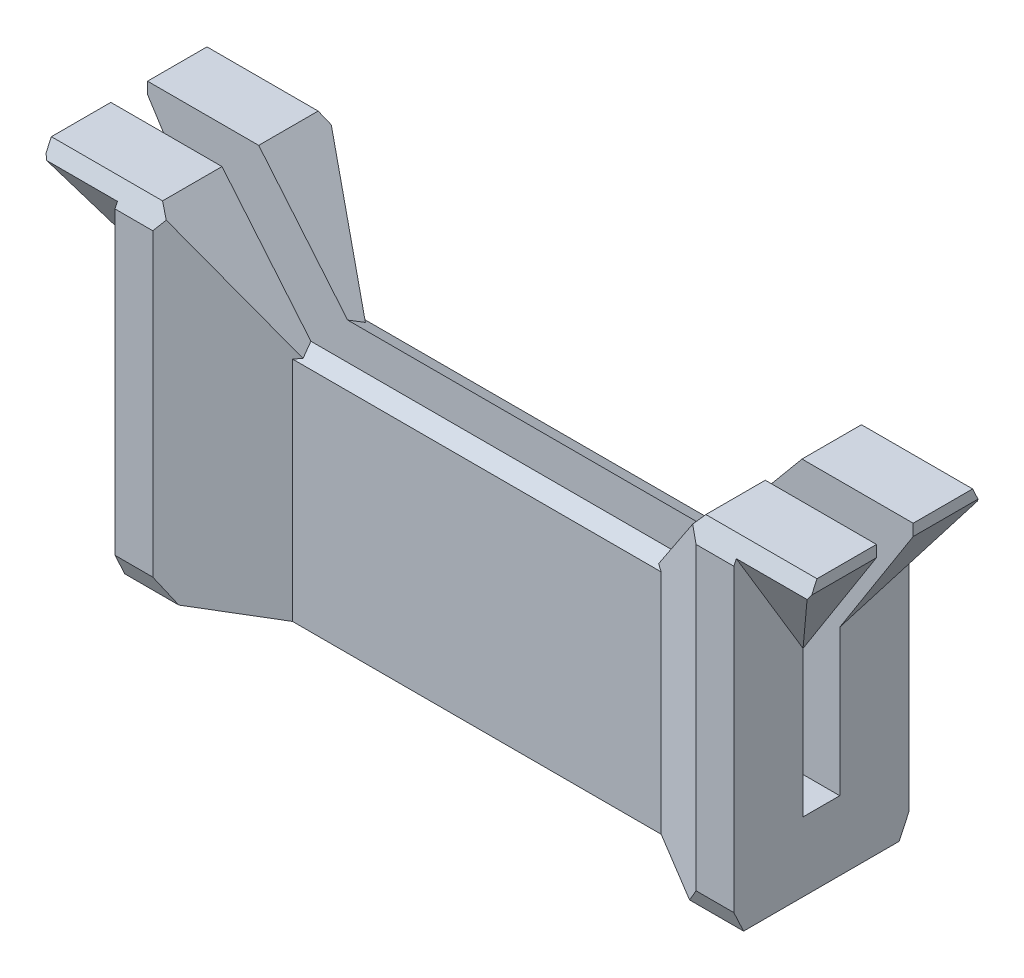
SolidWorks part; units mm, degrees
material "ABS"
ref_plane "Alzado" through (0, 0, 0) normal (0, 0, 1) x (1, 0, 0)
ref_plane "Planta" through (0, 0, 0) normal (0, 1, 0) x (1, 0, 0)
ref_plane "Vista lateral" through (0, 0, 0) normal (1, 0, 0) x (0, 0, -1)
sketch "Croquis2" plane through (0, 0, 0) normal (1, 0, 0) x (0, 0, -1)
  line L0 (-0.875, 0) -> (0.875, 0)
  line L1 (0.875, 0) -> (0.875, 13)
  line L2 (0.875, 13) -> (4.175, 13)
  line L3 (4.175, 13) -> (4.175, 2.1921)
  line L4 (4.175, 2.1921) -> (0.875, -3.3)
  line L5 (-0.875, -3.3) -> (0.875, -3.3)
  line L6 (0, -3.3) -> (0, 0) construction
  line L7 (-4.175, 2.1921) -> (-0.875, -3.3)
  line L8 (-4.175, 13) -> (-4.175, 2.1921)
  line L9 (-0.875, 13) -> (-4.175, 13)
  line L10 (-0.875, 0) -> (-0.875, 13)
  line L11 (4.175, 2.1921) -> (4.175, -3.3)
  line L12 (4.175, -3.3) -> (0.875, -3.3)
  line L13 (-0.875, -3.3) -> (-4.175, -3.3)
  line L14 (-4.175, -3.3) -> (-4.175, 2.1921)
  dimension "D1" = 1.75
  dimension "D3" = 13
  dimension "D4" = 62
  dimension "D5" = 1.75
  dimension "D6" = 3.3
extrude "Saliente-Extruir1" add sketch "Croquis2" along normal mid plane 36.5 contours L6 L5 L4 L3 L2 L1 L0 | L5 L6 L0 L10 L9 L8 L7 | L14 L13 L7 | L12 L11 L4
sketch "Croquis3" plane through (18.25, 0, 0) normal (1, 0, 0) x (0, 0, -1)
  line L0 (0.6, 1) -> (-0.6, 1)
  line L1 (-0.6, 1) -> (-0.6, 6.5)
  line L2 (-0.6, 6.5) -> (-4.175, 12.4498)
  line L3 (-4.175, 12.4498) -> (-4.175, 13)
  line L4 (-4.175, 13) -> (-4.175, -3.3) construction
  line L5 (-0.875, 0) -> (0.875, 0) construction
  line L6 (-4.175, 13) -> (-4.175, -3.3)
  line L8 (-4.175, -3.3) -> (4.175, -3.3)
  line L10 (0, -3.3) -> (0, 1) construction
  line L12 (4.175, 13) -> (4.175, -3.3)
  line L14 (4.175, 12.4498) -> (4.175, 13)
  line L15 (0.6, 6.5) -> (4.175, 12.4498)
  line L16 (0.6, 1) -> (0.6, 6.5)
  line M23 (0.875, 0) -> (-0.875, 0)
  line M24 (-0.875, 0) -> (-0.875, 13)
  line M26 (-4.175, 13) -> (-4.175, -3.3)
  line M27 (-4.175, -3.3) -> (4.175, -3.3)
  line M28 (4.175, -3.3) -> (4.175, 13)
  line M30 (0.875, 13) -> (0.875, 0)
  dimension "D1" = 1.2
  dimension "D2" = 5.5
  dimension "D3" = 1
  dimension "D4" = 62
extrude "Cortar-Extruir1" cut sketch "Croquis3" against normal blind 1.7 from offset 1.8 contours L10 L2 M27 M23 M24 M26 | L10 L8 L15 M28 M30 M23 offset against normal yes
mirror "Simetría1" about plane through (0, 0, 0) normal (1, 0, 0) of "Cortar-Extruir1"
sketch "Croquis4" plane through (0, 13, 0) normal (0, 1, 0) x (1, 0, 0)
  line L0 (8.7893, -1.675) -> (-8.7893, -1.675)
  line L1 (-8.7893, -1.675) -> (-12.95, -4.175)
  line L2 (18.25, -4.175) -> (-18.25, -4.175) construction
  line L3 (-12.95, -4.175) -> (12.95, -4.175)
  line L4 (0, -4.175) -> (0, -1.675) construction
  line L5 (8.7893, -1.675) -> (12.95, -4.175)
  line L6 (0, 0) -> (5.3382, 0) construction
  line L7 (8.7893, 1.675) -> (12.95, 4.175)
  line L8 (-12.95, 4.175) -> (12.95, 4.175)
  line L9 (-8.7893, 1.675) -> (-12.95, 4.175)
  line L10 (8.7893, 1.675) -> (-8.7893, 1.675)
  line L11 (18.25, -0.875) -> (-18.25, -0.875) construction
  line L12 (-12.95, -4.175) -> (23.55, -4.175) construction
  line L13 (18.25, -4.175) -> (-18.25, -4.175) construction
  line L14 (-12.95, -4.175) -> (-14.75, -4.175) construction
  line L15 (18.25, -4.175) -> (-18.25, -4.175) construction
  line L16 (-16.45, -4.175) -> (-18.25, -4.175) construction
  dimension "D1" = 0.8
  dimension "D2" = 62
extrude "Cortar-Extruir2" cut sketch "Croquis4" against normal through all
sketch "Croquis5" plane through (0, 0, 4.175) normal (0, 0, 1) x (1, 0, 0)
  line L0 (-12.95, 13) -> (12.95, 13)
  line L1 (0, 13) -> (0, 8) construction
  line L2 (8.7893, 8) -> (-8.7893, 8)
  line L3 (-8.7893, 8) -> (-12.95, 13)
  line L4 (-8.7893, -3.3) -> (-8.7893, 13) construction
  line L5 (8.7893, 8) -> (12.95, 13)
  dimension "D1" = 5
extrude "Cortar-Extruir3" cut sketch "Croquis5" against normal through all
sketch "Croquis6" plane through (14.75, 0, 0) normal (1, 0, 0) x (0, 0, -1)
  line L8 (-4.175, -3.3) -> (4.175, -3.3)
  line L9 (-4.175, -3.3) -> (4.175, -3.3)
  line L10 (4.175, 12.4498) -> (0.875, 6.9577)
  line L11 (0.875, 6.9577) -> (0.875, 0)
  line L12 (0.875, 0) -> (-0.875, 0)
  line L13 (-0.875, 0) -> (-0.875, 6.9577)
  line L14 (-0.875, 6.9577) -> (-4.175, 12.4498)
  line L15 (4.175, -3.3) -> (4.175, 12.4498)
  line L16 (4.175, -3.3) -> (4.175, 12.4498)
  line L17 (-4.175, 12.4498) -> (-4.175, -3.3)
  line L18 (4.175, 12.4498) -> (0.875, 6.9577)
  line L19 (0.875, 6.9577) -> (0.875, 0)
  line L20 (0.875, 0) -> (-0.875, 0)
  line L21 (-0.875, 0) -> (-0.875, 6.9577)
  line L22 (-0.875, 6.9577) -> (-4.175, 12.4498)
  line L23 (-4.175, 12.4498) -> (-4.175, -3.3)
  dimension "D1" = 0
extrude "Cortar-Extruir4" cut sketch "Croquis6" along normal up to next
mirror "Simetría2" about plane through (0, 0, 0) normal (1, 0, 0) of "Cortar-Extruir4"
sketch "Croquis7" plane through (0, 0, -4.175) normal (0, 0, -1) x (-1, 0, 0)
  line L0 (14.75, 6.9577) -> (18.25, 12.4498)
  line L1 (18.25, 12.4498) -> (18.25, 6.9577)
  line L2 (18.25, 6.9577) -> (14.75, 6.9577)
  line L4 (0, 0) -> (0, 13.5433) construction
  line L5 (-18.25, 6.9577) -> (-14.75, 6.9577)
  line L6 (-18.25, 12.4498) -> (-18.25, 6.9577)
  line L7 (-14.75, 6.9577) -> (-18.25, 12.4498)
extrude "Cortar-Extruir5" cut sketch "Croquis7" against normal blind 10
chamfer "Chaflán2" distance 1 angle 25 10 edges at (0, 8, 1.675) (0, 8, -1.675) (15.6, 13, 4.175) (-15.6, 13, 4.175) (-15.6, 13, -4.175) (15.6, 13, -4.175) (-13.85, -3.3, -4.175) (-13.85, -3.3, 4.175) (13.85, -3.3, 4.175) (13.85, -3.3, -4.175)
sketch "Croquis8" plane through (-14.75, 0, 0) normal (-1, 0, 0) x (0, 0, 1)
  line L0 (1.675, -3.3) -> (4.175, -3.3)
  line L1 (3.7087, -3.3) -> (-3.7087, -3.3) construction
  line L2 (4.175, -3.3) -> (4.175, 0.8607)
  line L3 (4.175, 0.8607) -> (1.675, -3.3)
  line L4 (0, 0) -> (0, -2.3333) construction
  line L5 (-0.875, 0) -> (0.875, 0) construction
  line L6 (-4.175, 0.8607) -> (-1.675, -3.3)
  line L7 (-4.175, -3.3) -> (-4.175, 0.8607)
  line L8 (-1.675, -3.3) -> (-4.175, -3.3)
  line L9 (-4.175, -2.3) -> (-4.175, 12) construction
  dimension "D1" = 62
extrude "Cortar-Extruir6" [suppressed] cut sketch "Croquis8" against normal through all
